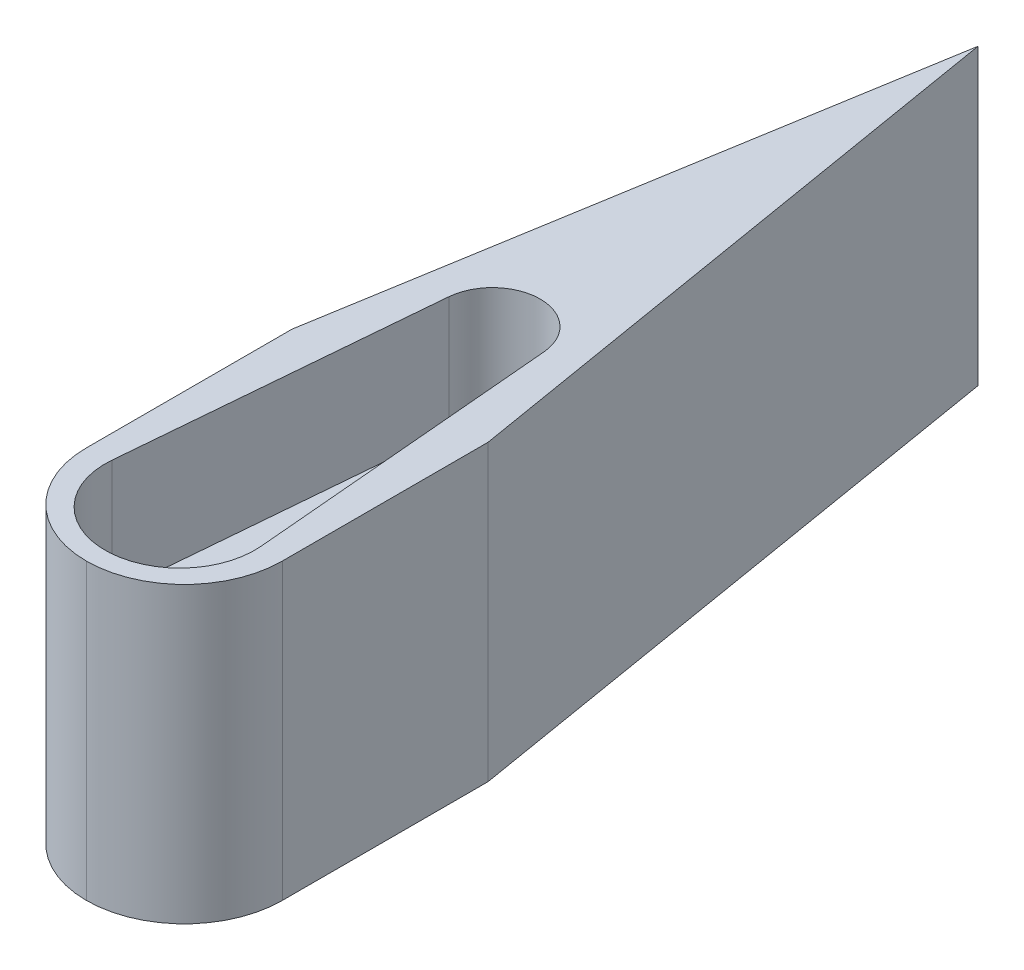
SolidWorks part; units mm, degrees
material "1023 Carbon Steel Sheet (SS)"
ref_plane "Front Plane" through (0, 0, 0) normal (0, 0, 1) x (1, 0, 0)
ref_plane "Top Plane" through (0, 0, 0) normal (0, 1, 0) x (1, 0, 0)
ref_plane "Right Plane" through (0, 0, 0) normal (1, 0, 0) x (0, 0, -1)
sketch "Sketch1" plane through (0, 0, 0) normal (0, 1, 0) x (1, 0, 0)
  line L0 (0, 0) -> (0, 38.1) construction
  line L1 (0, 38.1) -> (-6.35, 0)
  line L2 (0, 38.1) -> (6.35, 0)
  line L3 (-6.35, 0) -> (-6.35, -19.685)
  line L4 (-6.35, -19.685) -> (6.35, -19.685)
  line L5 (6.35, 0) -> (6.35, -19.685)
  dimension "D1" = 38.1
  dimension "D2" = 6.35
  dimension "D3" = 6.35
  dimension "D4" = 19.685
  dimension "D5" = 12.7
extrude "Boss-Extrude1" add sketch "Sketch1" along normal blind 19.05
fillet "Fillet1" radius 6.35 2 edges at (-6.35, 9.525, 19.685) (6.35, 9.525, 19.685)
sketch "Sketch3" plane through (0, 19.05, 0) normal (0, 1, 0) x (1, 0, 0)
  line L2 (2.9888, 6.8876) -> (4.7322, -13.2112)
  line L3 (-4.7322, -13.2112) -> (-2.9888, 6.8876)
  line L8 (-6.35, 0) -> (-6.35, -13.335)
  line L9 (6.35, -13.335) -> (6.35, 0)
  line L10 (6.35, 0) -> (0, 38.1)
  line L11 (0, 38.1) -> (-6.35, 0)
  circle A2 centre (0, 6.6283) radius 1.6
  circle A4 centre (0, 6.6283) radius 3
  arc A8 (-6.35, -13.335) -> (0, -19.685) centre (0, -13.335) ccw
  arc A9 (0, -19.685) -> (6.35, -13.335) centre (0, -13.335) ccw
  circle A10 centre (0, -13.6217) radius 2.5
  circle A12 centre (0, -13.6217) radius 4.75
  circle A14 centre (0, 2.6283) radius 1.6
sketch "Sketch4" plane through (0, 19.05, 0) normal (0, 1, 0) x (1, 0, 0)
  line L1 (-4.7322, -13.2112) -> (-2.9888, 6.8876)
  line L2 (2.9888, 6.8876) -> (4.7322, -13.2112)
  line L3 (-4.8319, -13.2025) -> (-3.0884, 6.8963)
  line L4 (-6.35, 0) -> (-6.35, -13.335)
  line L5 (6.35, -13.335) -> (6.35, 0)
  line L6 (6.35, 0) -> (0, 38.1)
  line L7 (0, 38.1) -> (-6.35, 0)
  line L8 (-6.35, 0) -> (-6.35, -13.335)
  line L9 (6.35, -13.335) -> (6.35, 0)
  line L10 (6.35, 0) -> (0, 38.1)
  line L11 (0, 38.1) -> (-6.35, 0)
  line L12 (3.0884, 6.8963) -> (4.8319, -13.2025)
  arc A0 (-2.9888, 6.8876) -> (2.9888, 6.8876) centre (0, 6.6283) cw
  arc A1 (4.7322, -13.2112) -> (-4.7322, -13.2112) centre (0, -13.6217) cw
  arc A2 (-6.35, -13.335) -> (0, -19.685) centre (0, -13.335) ccw
  arc A3 (0, -19.685) -> (6.35, -13.335) centre (0, -13.335) ccw
  arc A4 (-6.35, -13.335) -> (0, -19.685) centre (0, -13.335) ccw
  arc A5 (0, -19.685) -> (6.35, -13.335) centre (0, -13.335) ccw
  arc A6 (4.8319, -13.2025) -> (-4.8319, -13.2025) centre (0, -13.6217) cw
  arc A7 (-3.0884, 6.8963) -> (3.0884, 6.8963) centre (0, 6.6283) cw
  dimension "D2" = 0.1
  dimension "D1" = 0
extrude "Cut-Extrude1" cut sketch "Sketch4" against normal blind 7.5 contours L3 A7 L12 A6
